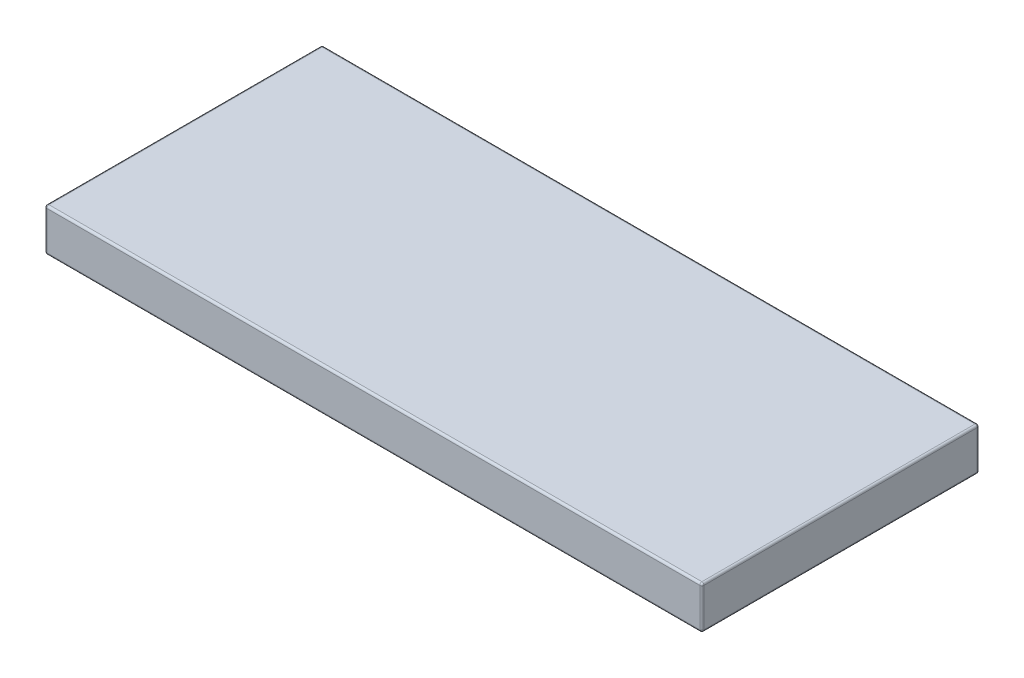
SolidWorks part; units mm, degrees
ref_plane "Front Plane" through (0, 0, 0) normal (0, 0, 1) x (1, 0, 0)
ref_plane "Top Plane" through (0, 0, 0) normal (0, 1, 0) x (1, 0, 0)
ref_plane "Right Plane" through (0, 0, 0) normal (1, 0, 0) x (0, 0, -1)
sketch "Sketch1" plane through (0, 0, 0) normal (0, 1, 0) x (1, 0, 0)
  line L1 (77, 32.5) -> (-77, 32.5)
  line L2 (77, 32.5) -> (77, -32.5)
  line L3 (77, -32.5) -> (-77, -32.5)
  line L4 (-77, 32.5) -> (-77, -32.5)
  line L5 (77, 32.5) -> (-77, -32.5) construction
  line L6 (77, -32.5) -> (-77, 32.5) construction
  point P0 (0, 0)
  dimension "D1" = 154
  dimension "D2" = 65
extrude "base" add sketch "Sketch1" along normal blind 10 contours L1 L4 L3 L2
sketch "Sketch2" plane through (0, 0, 0) normal (0, -1, 0) x (1, 0, 0)
  circle A0 centre (0, 0) radius 3
  dimension "D1" = 6
extrude "load cell button cut" [suppressed] cut sketch "Sketch2" against normal blind 2
sketch "Sketch4" plane through (0, 0, 0) normal (1, 0, 0) x (0, 0, -1)
  line L0 (3, 0) -> (3, 2)
  line L1 (3, 2) -> (0, 3.7321)
  line L2 (0, 3.7321) -> (0, 0) construction
  line L3 (0, 0) -> (3, 0)
  line L4 (0, 3.7321) -> (0, 0)
  dimension "D1" = 3
  dimension "D2" = 2
  dimension "D3" = 60
revolve "Cut-Revolve1" [suppressed] cut sketch "Sketch4" angle 360 about L2
fillet "Fillet1" radius 0.5 12 edges at (77, 5, -32.5) (-77, 5, -32.5) (-77, 5, 32.5) (77, 5, 32.5) (0, 10, -32.5) (-77, 10, 0) (0, 10, 32.5) (77, 10, 0) (0, 0, -32.5) (-77, 0, 0) (0, 0, 32.5) (77, 0, 0)
equation "\"D2@Sketch1\"=65"
equation "\"D1@Sketch1\"=144+10"
